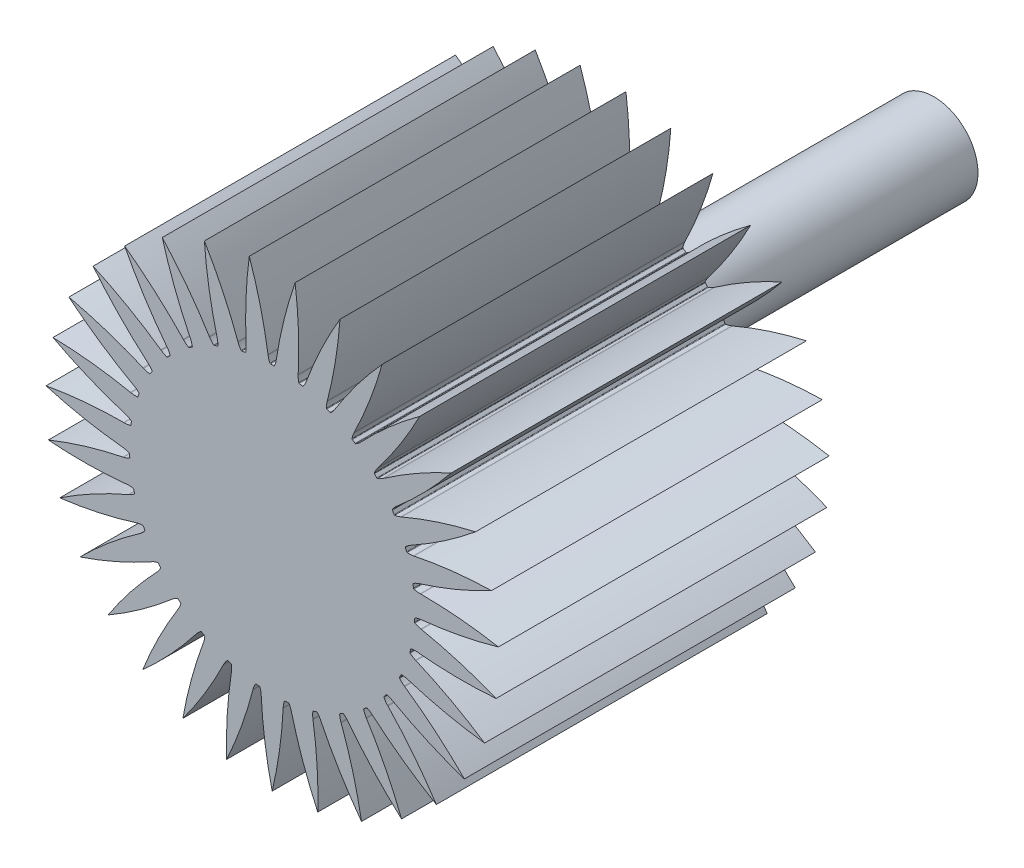
SolidWorks part; units mm, degrees
material "Pure Gold"
ref_plane "Front" through (0, 0, 0) normal (0, 0, 1) x (1, 0, 0)
ref_plane "Top" through (0, 0, 0) normal (0, 1, 0) x (1, 0, 0)
ref_plane "Right" through (0, 0, 0) normal (1, 0, 0) x (0, 0, -1)
sketch "Sketch1" plane through (0, 0, 0) normal (0, 0, 1) x (1, 0, 0)
  line L0 (0, 0) -> (0, 500) construction
  circle A1 centre (0, 0) radius 500
  dimension "D1" = 1000
extrude "Extrude1" add sketch "Sketch1" along normal blind 300
sketch "Sketch2" plane through (0, 0, 300) normal (0, 0, 1) x (1, 0, 0)
  line L0 (0, 0) -> (0, 500) construction
  line L1 (3.7322, 135.1942) -> (3.81, 135.7022)
  line L2 (-3.7322, 135.1942) -> (-3.81, 135.7022)
  circle A0 centre (0, 0) radius 500 construction
  arc A1 (1.905, 129.3522) -> (-1.905, 129.3522) centre (0, 0) ccw
  arc A2 (1.905, 129.3522) -> (3.7322, 135.1942) centre (-16.3537, 138.2697) ccw
  arc A3 (3.81, 135.7022) -> (241.2315, 437.9582) centre (390.2485, 76.5306) cw
  arc A4 (-3.81, 135.7022) -> (-241.2315, 437.9582) centre (-390.2485, 76.5306) ccw
  arc A5 (-1.905, 129.3522) -> (-3.7322, 135.1942) centre (16.3537, 138.2697) cw
  dimension "D1" = 7.62
  dimension "D2" = 20.32
  dimension "D4" = 6.35
  dimension "D5" = 3.81
  dimension "D6" = 129.3662
  dimension "D7" = 390.9425
  dimension "D3" = 0.508
extrude "Cut-Extrude1" cut sketch "Sketch2" against normal through all and the other way through all flip side to cut
fillet "Fillet1" radius 0.635 2 edges at (1.905, 129.3522, 150) (-1.905, 129.3522, 150)
pattern_circular "CirPattern1" count 31 over 360 about axis through (0, 0, 300) along (0, 0, -1) of "Cut-Extrude1", "Fillet1"
sketch "Sketch3" plane through (0, 0, 0) normal (0, 0, -1) x (-1, 0, 0)
  circle A0 centre (0, 0) radius 40
  dimension "D1" = 80
extrude "Extrude2" add sketch "Sketch3" along normal blind 300
equation "\"wheelSize\"= 100cm"
equation "\"D1@Sketch1\"=\"wheelSize\""
equation "\"D1@Sketch3\" = \"HoleMountDiameter@PrintingPress.Assembly\""
equation "\"D1@Extrude2\" = 3 * \"RivetLength@PrintingPress.Assembly\""
equation "\"wheelThickness\"= 3 * \"RivetLength@PrintingPress.Assembly\""
equation "\"D1@Extrude1\"=\"wheelThickness\""
